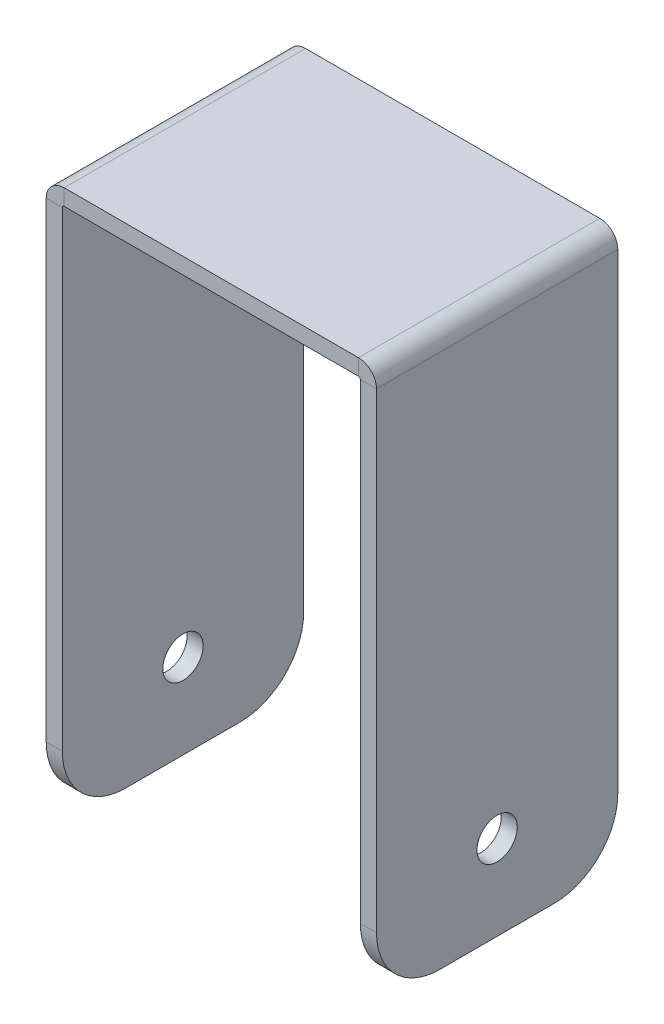
SolidWorks part; units mm, degrees
note: The reader was unsure of these and kept them because the rebuilt part matched: thickness of "Base-Flange1", "Edge-Flange1", "Sheet-Metal2", "Sheet-Metal3", "Sheet-Metal7"; flange length of "Edge-Flange1".
ref_plane "Front Plane" through (0, 0, 0) normal (0, 0, 1) x (1, 0, 0)
ref_plane "Top Plane" through (0, 0, 0) normal (0, 1, 0) x (1, 0, 0)
ref_plane "Right Plane" through (0, 0, 0) normal (1, 0, 0) x (0, 0, -1)
sketch "Sketch3" plane through (0, 0, 0) normal (0, 1, 0) x (1, 0, 0)
  line L1 (-65, 47.5) -> (65, 47.5)
  line L2 (-65, 47.5) -> (-65, -47.5)
  line L3 (-65, -47.5) -> (65, -47.5)
  line L4 (65, 47.5) -> (65, -47.5)
  line L5 (-65, 47.5) -> (65, -47.5) construction
  line L6 (-65, -47.5) -> (65, 47.5) construction
  point P0 (0, 0)
  dimension "D1" = 130
  dimension "D2" = 95
base flange "Base-Flange1" sketch "Sketch3" thickness 6.35 reverse thickness direction no parameters "D1"=0.7366
edge flange "Edge-Flange1" sketch "Sketch12" flange angle 90 flange length 217.4875 flange position material inside bend radius 0.7366 thickness 6.35 relief rectangular parameters "D6"=10
sketch "Sketch12" plane through (65, -6.35, 0) normal (-1, 0, 0) x (0, 0, -1)
  line L0 (47.5, 0) -> (-47.5, 0) construction
  line L2 (-47.5, 0) -> (-47.5, 211.1375)
  line L3 (-47.5, 211.1375) -> (47.5, 211.1375)
  line L4 (47.5, 211.1375) -> (47.5, 0)
  line L5 (47.5, 0) -> (-47.5, 0)
  line L6 (-47.5, 177.8) -> (47.5, 177.8) construction
  line L7 (0, 185.7375) -> (-47.5, 185.7375) construction
  circle A0 centre (0, 177.8) radius 7.9375
  dimension "D2" = 177.8
  dimension "D3" = 15.875
  dimension "D1" = 25.4
bend "EdgeBend1" bend radius 0.7366 bend angle 90 parameters "D5"=1
mirror "Mirror1" about plane through (0, 0, 0) normal (1, 0, 0) of "Edge-Flange1"
bend "MirrorBend1" bend radius 0.7366 bend angle 90 parameters "D5"=2
fillet "Fillet1" radius 25 4 edges at (-61.825, -217.4875, 47.5) (-61.825, -217.4875, -47.5) (61.825, -217.4875, -47.5) (61.825, -217.4875, 47.5)
sketch "Bend-Lines1" [suppressed] plane through (0, 0, 0) normal (0, 1, 0) x (1, 0, 0)
sketch "Bounding-Box1" [suppressed] plane through (0, 0, 0) normal (0, 1, 0) x (1, 0, 0)
sheet metal parameters "Sheet-Metal2" thickness 6.35 parameters "D1"=0.7366, "D7"=0.7366
flat pattern "Flat-Pattern2" [suppressed]
sketch "Bend-Lines2" plane through (0, 0, 0) normal (0, 1, 0) x (1, 0, 0)
sketch3d "Bounding-Box2" [suppressed]
  line L0 (-70, 35, 0) -> (70, 35, 0) construction
  line L1 (-70, -35, 0) -> (70, -35, 0) construction
  line L2 (-70, 35, 0) -> (-70, -35, 0) construction
  line L3 (70, 35, 0) -> (70, -35, 0) construction
sheet metal parameters "Sheet-Metal3" thickness 6.35 parameters "D1"=0.7366, "D7"=0.7366
flat pattern "Flat-Pattern2"
sketch "Bend-Lines2" plane through (0, 0, 0) normal (0, 1, 0) x (1, 0, 0)
  line L0 (40.9856, -42.5) -> (40.9856, 42.5) construction
  line L1 (40.9856, -42.5) -> (40.9856, 42.5) construction
sketch3d "Bounding-Box2" [suppressed]
  line L0 (243.3211, 42.5, 0) -> (-45, 42.5, 0) construction
  line L1 (243.3211, -42.5, 0) -> (-45, -42.5, 0) construction
  line L2 (243.3211, 42.5, 0) -> (243.3211, -42.5, 0) construction
  line L3 (-45, 42.5, 0) -> (-45, -42.5, 0) construction
bend of the flat pattern "Flatten-<EdgeBend1>1"
sheet metal parameters "Sheet-Metal7" thickness 6.35 parameters "D1"=0.7366, "D7"=0.7366
flat pattern "Flat-Pattern2"
sketch "Bend-Lines2" plane through (0, 0, 0) normal (0, 1, 0) x (1, 0, 0)
  line L0 (60.9856, -47.5) -> (60.9856, 47.5) construction
  line L1 (60.9856, -47.5) -> (60.9856, 47.5) construction
  line L2 (-60.9856, 47.5) -> (-60.9856, -47.5) construction
  line L3 (-60.9856, 47.5) -> (-60.9856, -47.5) construction
sketch3d "Bounding-Box2" [suppressed]
  line L0 (-274.4586, 47.5, 0) -> (274.4586, 47.5, 0) construction
  line L1 (-274.4586, -47.5, 0) -> (274.4586, -47.5, 0) construction
  line L2 (-274.4586, 47.5, 0) -> (-274.4586, -47.5, 0) construction
  line L3 (274.4586, 47.5, 0) -> (274.4586, -47.5, 0) construction
bend of the flat pattern "Flatten-<EdgeBend1>1"
bend of the flat pattern "Flatten-<MirrorBend1>1"
